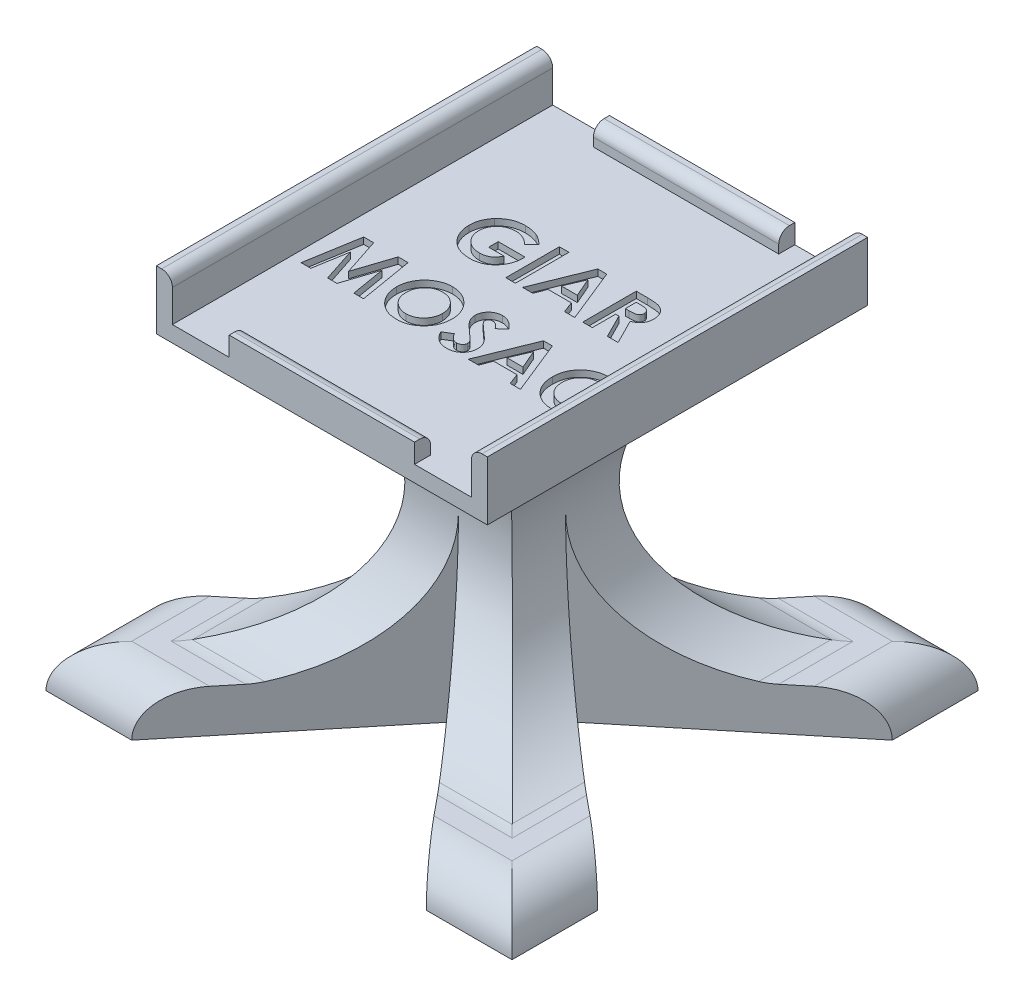
SolidWorks part; units mm, degrees
note: The reader was unsure of these and kept them because the rebuilt part matched: shared geometry of "Sketch1<3>", "Sketch1<4>", "Sketch4<3>".
ref_plane "Front Plane" through (0, 0, 0) normal (0, 0, 1) x (1, 0, 0)
ref_plane "Top Plane" through (0, 0, 0) normal (0, 1, 0) x (1, 0, 0)
ref_plane "Right Plane" through (0, 0, 0) normal (1, 0, 0) x (0, 0, -1)
sketch "Sketch1" plane through (0, 0, 0) normal (0, 1, 0) x (1, 0, 0)
  line L0 (-69.75, 81.25) -> (69.75, 81.25)
  line L1 (-67.25, 78.75) -> (67.25, 78.75) construction
  line L2 (-67.25, 78.75) -> (-67.25, -78.75) construction
  line L3 (-67.25, -78.75) -> (67.25, -78.75) construction
  line L4 (67.25, 78.75) -> (67.25, -78.75) construction
  line L5 (-67.25, 78.75) -> (67.25, -78.75) construction
  line L6 (-67.25, -78.75) -> (67.25, 78.75) construction
  line L7 (69.75, 81.25) -> (69.75, -81.25)
  line L8 (-69.75, -81.25) -> (69.75, -81.25)
  line L9 (-69.75, 81.25) -> (-69.75, -81.25)
  line L10 (-77.25, 88.75) -> (77.25, 88.75)
  line L11 (77.25, 88.75) -> (77.25, -88.75)
  line L12 (-77.25, -88.75) -> (77.25, -88.75)
  line L13 (-77.25, 88.75) -> (-77.25, -88.75)
  point P0 (0, 0)
  dimension "D1" = 134.5
  dimension "D2" = 157.5
  dimension "D3" = 2.5
  dimension "D4" = 7.5
extrude "Boss-Extrude1" add sketch "Sketch1" along normal blind 7.5 contours L10 L13 L12 L11 L9 L0 L7 L8 | L0 L9 L8 L7
extrude "Boss-Extrude2" add sketch "Sketch1<3>" along normal blind 20 from surface at 7.5 starting at face at (0, 7.5, 0)
sketch "Sketch1<3>" plane through (0, 0, 0) normal (0, 1, 0) x (1, 0, 0) same geometry as "Sketch1"
sketch "Sketch5" plane through (0, 0, -81.25) normal (0, 0, 1) x (1, 0, 0)
  line L7 (-69.75, 27.5) -> (69.75, 27.5) construction
  line L8 (-69.75, 7.5) -> (-43.25, 7.5)
  line L9 (-69.75, 7.5) -> (-69.75, 27.5)
  line L10 (-69.75, 27.5) -> (-43.25, 27.5)
  line L11 (-43.25, 7.5) -> (-43.25, 27.5)
  line L13 (69.75, 7.5) -> (43.25, 7.5)
  line L14 (69.75, 7.5) -> (69.75, 27.5)
  line L15 (69.75, 27.5) -> (43.25, 27.5)
  line L16 (43.25, 7.5) -> (43.25, 27.5)
  dimension "D1" = 26.5
extrude "Cut-Extrude4" cut sketch "Sketch5" against normal up to next and the other way up to next
sketch "Sketch6" plane through (0, 27.5, 0) normal (0, 1, 0) x (1, 0, 0)
  line L0 (43.25, 88.75) -> (-43.25, 88.75) construction
  line L1 (-43.25, 88.75) -> (-43.25, 81.25) construction
  line L2 (-43.25, 81.25) -> (43.25, 81.25) construction
  line L3 (43.25, 81.25) -> (43.25, 88.75) construction
  line L4 (43.25, -88.75) -> (43.25, -81.25) construction
  line L5 (43.25, -81.25) -> (-43.25, -81.25) construction
  line L6 (-43.25, -81.25) -> (-43.25, -88.75) construction
  line L7 (-43.25, -88.75) -> (43.25, -88.75) construction
  line L8 (43.25, 88.75) -> (-43.25, 88.75)
  line L9 (-43.25, 88.75) -> (-43.25, 81.25)
  line L10 (-43.25, 81.25) -> (43.25, 81.25)
  line L11 (43.25, 81.25) -> (43.25, 88.75)
  line L12 (43.25, -88.75) -> (43.25, -81.25)
  line L13 (43.25, -81.25) -> (-43.25, -81.25)
  line L14 (-43.25, -81.25) -> (-43.25, -88.75)
  line L15 (-43.25, -88.75) -> (43.25, -88.75)
extrude "Cut-Extrude5" cut sketch "Sketch6" against normal offset from surface (11 mm away) 9 up to face at (0, 7.5, 0)
sketch "Sketch7" plane through (0, 7.5, 0) normal (0, 1, 0) x (1, 0, 0)
  line L0 (-69.75, 8) -> (69.75, 8) construction
  line L1 (-69.75, -88.75) -> (-69.75, 88.75) construction
  line L2 (69.75, 88.75) -> (69.75, -88.75) construction
  text T0 "GIAR\r\nMOSAC" font "Century Gothic" height 25
  dimension "D1" = 8
extrude "Cut-Extrude6" cut sketch "Sketch7" against normal blind 3
fillet "Fillet2" radius 5 4 edges at (0, 16.5, -81.25) (0, 16.5, 81.25) (69.75, 27.5, 0) (-69.75, 27.5, 0)
extrude "Boss-Extrude3" add sketch "Sketch1<4>" against normal blind 150 contours L10 L13 L12 L11 L9 L0 L7 L8 | L0 L9 L8 L7
sketch "Sketch1<4>" plane through (0, 0, 0) normal (0, 1, 0) x (1, 0, 0) same geometry as "Sketch1"
sketch "Sketch2" plane through (0, 0, 88.75) normal (0, 0, 1) x (1, 0, 0)
  line L0 (-77.25, 27.5) -> (-77.25, -150) construction
  line L1 (-77.25, -150) -> (77.25, -150) construction
  line L2 (-25, 38.9917) -> (-25, -188.9917) construction
  line L3 (-77.25, 0) -> (77.25, 0) construction
  line L4 (77.25, 27.5) -> (77.25, -150) construction
  line L5 (25, -12.4835) -> (25, -137.5165) construction
  line L6 (-25, 0) -> (25, 0) construction
  line L7 (-77.25, 0) -> (-77.25, -130)
  line L8 (77.25, 0) -> (77.25, -130)
  line L9 (-77.25, -130) -> (77.25, -130) construction
  arc A0 (-77.25, -130) -> (-77.25, 0) centre (-91.5556, -65) ccw
  arc A1 (77.25, 0) -> (77.25, -130) centre (91.5556, -65) ccw
  point P11 (-25, -65)
  point P20 (25, -65)
  point P24 (0, 0)
  dimension "D2" = 50
  dimension "D1" = 150
  dimension "D3" = 20
extrude "Cut-Extrude1" cut sketch "Sketch2" against normal up to next
sketch "Sketch3" plane through (-77.25, 0, 0) normal (-1, 0, 0) x (0, 0, 1)
  line L0 (-25, 0) -> (25, 0)
  line L1 (-88.75, 0) -> (88.75, 0) construction
  line L2 (-25, 38.9786) -> (-25, -188.9786) construction
  line L3 (25, 38.3971) -> (25, -188.3971) construction
  line L6 (-88.75, -130) -> (88.75, -130) construction
  line L11 (-88.75, 0) -> (-88.75, -150)
  line L12 (-88.75, -150) -> (-77.25, -150)
  line L13 (-88.75, -150) -> (88.75, -150) construction
  line L14 (-77.25, -150) -> (-77.25, -130)
  line L15 (88.75, 0) -> (88.75, -150)
  line L16 (88.75, -150) -> (77.25, -150)
  line L17 (77.25, -150) -> (77.25, -130)
  arc A0 (-88.75, 0) -> (-77.25, -130) centre (-90.7114, -65.6822) cw
  arc A1 (88.75, 0) -> (77.25, -130) centre (90.7114, -65.6822) ccw
  point P5 (0, 0)
  dimension "D2" = 154.5
  dimension "D1" = 50
extrude "Cut-Extrude2" cut sketch "Sketch3" against normal through all
sketch "Sketch4" plane through (0, -150, 0) normal (0, -1, 0) x (1, 0, 0)
  line L0 (-25.0035, 25) -> (25.0035, 25) construction
  line L1 (-108.75, -108.75) -> (108.75, -108.75) construction
  line L2 (-108.75, -108.75) -> (-108.75, 108.75) construction
  line L3 (-108.75, 108.75) -> (108.75, 108.75) construction
  line L4 (108.75, -108.75) -> (108.75, 108.75) construction
  line L5 (-108.75, -108.75) -> (108.75, 108.75) construction
  line L6 (-108.75, 108.75) -> (108.75, -108.75) construction
  line L7 (25, 25.0035) -> (25, -25.0035) construction
  line L8 (25.0035, -25) -> (-25.0035, -25) construction
  line L9 (-25, -25.0035) -> (-25, 25.0035) construction
  line L10 (-25.0035, 25) -> (25.0035, 25)
  line L11 (25, 25.0035) -> (25, -25.0035)
  line L12 (25.0035, -25) -> (-25.0035, -25)
  line L13 (-25, -25.0035) -> (-25, 25.0035)
  line L14 (-108.75, 108.75) -> (-68.75, 108.75)
  line L15 (-68.75, 108.75) -> (0, 25)
  line L16 (0, 25) -> (68.75, 108.75)
  line L17 (68.75, 108.75) -> (108.75, 108.75)
  line L18 (108.75, 108.75) -> (108.75, 68.75)
  line L19 (108.75, 68.75) -> (25, 0)
  line L20 (25, 0) -> (108.75, -68.75)
  line L21 (108.75, -68.75) -> (108.75, -108.75)
  line L22 (108.75, -108.75) -> (68.75, -108.75)
  line L23 (68.75, -108.75) -> (0, -25)
  line L24 (0, -25) -> (-68.75, -108.75)
  line L25 (-68.75, -108.75) -> (-108.75, -108.75)
  line L26 (-108.75, -108.75) -> (-108.75, -68.75)
  line L27 (-108.75, -68.75) -> (-25, 0)
  line L28 (-25, 0) -> (-108.75, 68.75)
  line L29 (-108.75, 68.75) -> (-108.75, 108.75)
  line L40 (-77.25, 77.25) -> (-77.25, -77.25)
  line L41 (-77.25, -77.25) -> (77.25, -77.25)
  line L42 (77.25, -77.25) -> (77.25, 77.25)
  line L43 (77.25, 77.25) -> (-77.25, 77.25)
  line L44 (-77.25, 42.8918) -> (-77.25, -42.8918)
  line L45 (-42.8918, -77.25) -> (42.8918, -77.25)
  line L46 (77.25, -42.8918) -> (77.25, 42.8918)
  line L47 (42.8918, 77.25) -> (-42.8918, 77.25)
  point P0 (0, 0)
  point P38 (0, 0)
  point P39 (0, -25)
  line M4 (77.25, -77.25) -> (77.25, 77.25)
  line M6 (-77.25, 77.25) -> (-77.25, -77.25)
  line M11 (-77.25, -77.25) -> (77.25, -77.25)
  line M12 (77.25, 77.25) -> (-77.25, 77.25)
  dimension "D1" = 217.5
  dimension "D2" = 217.5
  dimension "D3" = 40
  dimension "D4" = 0
extrude "Cut-Extrude3" cut sketch "Sketch4" against normal up to next contours L23 L24 M11 | L27 L28 M6 | L15 L16 M12 | L19 L20 M4
extrude "Boss-Extrude4" add sketch "Sketch4<3>" against normal up to vertex (20 mm away) contours L29 L28 L15 L14 M6 M12 | L19 L18 L17 L16 M12 M4 | L23 L22 L21 L20 M4 M11 | L27 L26 L25 L24 M11 M6
sketch "Sketch4<3>" plane through (0, -150, 0) normal (0, -1, 0) x (1, 0, 0) same geometry as "Sketch4"
fillet "Fillet1" radius 20 16 edges at (60.0709, -130, -77.25) (77.25, -130, -60.0709) (88.75, -130, -108.75) (108.75, -130, -88.75) (-88.75, -130, -108.75) (-108.75, -130, -88.75) (-60.0709, -130, -77.25) (-77.25, -130, -60.0709) (108.75, -130, 88.75) (88.75, -130, 108.75) (77.25, -130, 60.0709) (60.0709, -130, 77.25) (-77.25, -130, 60.0709) (-108.75, -130, 88.75) (-88.75, -130, 108.75) (-60.0709, -130, 77.25)
sketch "Sketch8" plane through (77.25, 0, 0) normal (1, 0, 0) x (0, 0, -1)
  line L4 (-88.75, 0) -> (88.75, 0)
  line L5 (88.75, 0) -> (88.75, 27.5)
  line L6 (88.75, 27.5) -> (-88.75, 27.5)
  line L7 (-88.75, 27.5) -> (-88.75, 0)
  line L8 (-88.75, 0) -> (88.75, 0)
  line L9 (88.75, 0) -> (88.75, 27.5)
  line L10 (88.75, 27.5) -> (-88.75, 27.5)
  line L11 (-88.75, 27.5) -> (-88.75, 0)
  dimension "D1" = 0
extrude "Cut-Extrude7" [suppressed] cut sketch "Sketch8" against normal through all
ref_plane "Plane2" [suppressed] through (0, -65, 0) normal (0, 1, 0) x (1, 0, 0)
split "Split1" [suppressed] bodies to split 114
